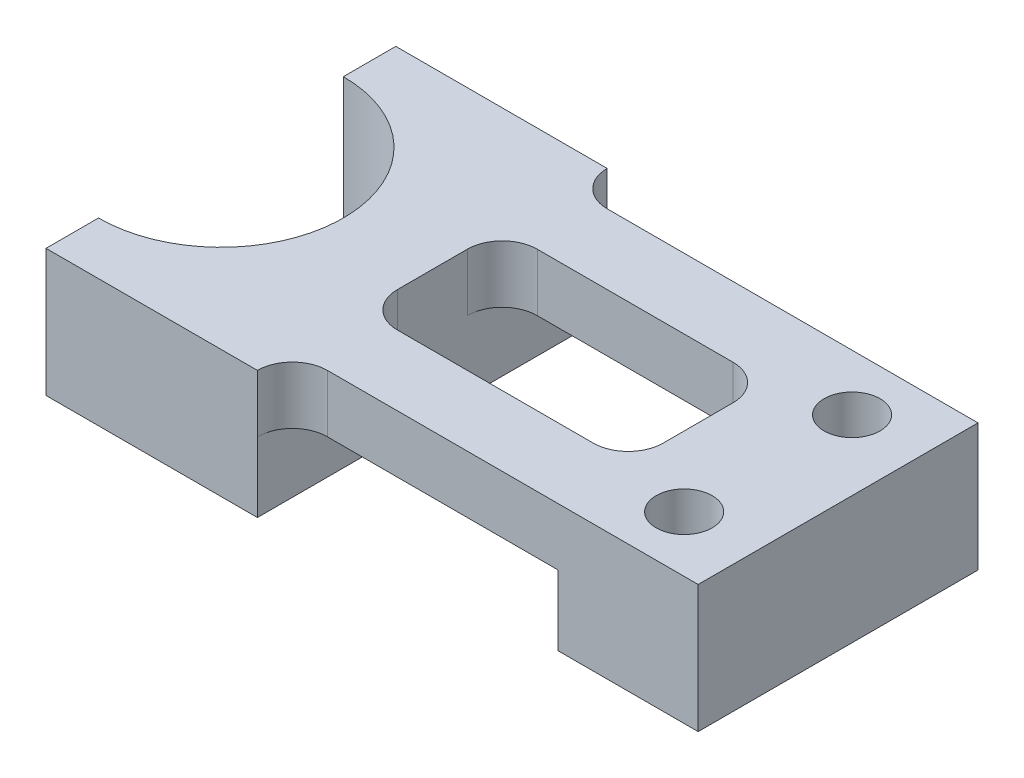
SolidWorks part; units mm, degrees
material "3.0205 (EN-AW 1200)"
ref_plane "Plan de face" through (0, 0, 0) normal (0, 0, 1) x (1, 0, 0)
ref_plane "Plan de dessus" through (0, 0, 0) normal (0, 1, 0) x (1, 0, 0)
ref_plane "Plan de droite" through (0, 0, 0) normal (1, 0, 0) x (0, 0, -1)
sketch "Esquisse1" plane through (0, 0, 0) normal (0, 1, 0) x (1, 0, 0)
  line L1 (-23.3581, -62.5798) -> (64.8619, -62.5798)
  line L2 (-23.3581, -62.5798) -> (-23.3581, -12.5798)
  line L3 (-23.3581, -12.5798) -> (64.8619, -12.5798)
  line L4 (64.8619, -62.5798) -> (64.8619, -12.5798)
  dimension "D1" = 88.22
  dimension "D2" = 50
extrude "Boss.-Extru.2" add sketch "Esquisse1" along normal blind 18.22
sketch "Esquisse3" plane through (0, 0, 0) normal (0, -1, 0) x (-1, 0, 0)
  line L0 (23.3581, -62.5798) -> (-64.8619, -62.5798) construction
  line L1 (-6.8619, -62.5798) -> (-44.8619, -62.5798)
  line L2 (-6.8619, -62.5798) -> (-6.8619, -12.5798)
  line L3 (-6.8619, -12.5798) -> (-44.8619, -12.5798)
  line L4 (-44.8619, -62.5798) -> (-44.8619, -12.5798)
  line L5 (-64.8619, -12.5798) -> (23.3581, -12.5798) construction
  dimension "D1" = 30.22
  dimension "D2" = 20
extrude "Enlèv. mat.-Extru.1" cut sketch "Esquisse3" against normal blind 10
sketch "Esquisse6" plane through (0, 0, 62.5798) normal (0, 0, 1) x (1, 0, 0)
  line L0 (-23.3581, 18.22) -> (64.8619, 18.22) construction
  line L1 (64.8619, 0) -> (6.8619, 0)
  line L2 (64.8619, 0) -> (64.8619, 18.22)
  line L3 (64.8619, 18.22) -> (6.8619, 18.22)
  line L4 (6.8619, 0) -> (6.8619, 18.22)
  line L5 (-23.3581, 18.22) -> (-23.3581, 0) construction
  dimension "D1" = 30.22
extrude "Enlèv. mat.-Extru.2" cut sketch "Esquisse6" against normal blind 5
sketch "Esquisse7" plane through (0, 0, 12.5798) normal (0, 0, -1) x (-1, 0, 0)
  line L0 (-64.8619, 18.22) -> (23.3581, 18.22) construction
  line L1 (-64.8619, 0) -> (-6.8619, 0)
  line L2 (-64.8619, 0) -> (-64.8619, 18.22)
  line L3 (-64.8619, 18.22) -> (-6.8619, 18.22)
  line L4 (-6.8619, 0) -> (-6.8619, 18.22)
  dimension "D1" = 30.22
extrude "Enlèv. mat.-Extru.3" cut sketch "Esquisse7" against normal blind 5
fillet "Congé6" radius 5 1 edges at (6.8619, 14.11, 17.5798)
fillet "Congé11" radius 5 1 edges at (6.8619, 14.11, 57.5798)
sketch "Esquisse8" plane through (0, 18.22, 0) normal (0, 1, 0) x (1, 0, 0)
  line L0 (-23.3581, -12.5798) -> (-23.3581, -62.5798) construction
  circle A0 centre (-23.3581, -37.5798) radius 17.5
  dimension "D2" = 35
  dimension "D1" = 25
extrude "Enlèv. mat.-Extru.4" cut sketch "Esquisse8" against normal through all
sketch "Esquisse10" plane through (0, 18.22, 0) normal (0, 1, 0) x (1, 0, 0)
  line L0 (64.8619, -57.5798) -> (64.8619, -17.5798) construction
  line L1 (44.8619, -47.5798) -> (6.8619, -47.5798)
  line L2 (44.8619, -47.5798) -> (44.8619, -27.5798)
  line L3 (44.8619, -27.5798) -> (6.8619, -27.5798)
  line L4 (6.8619, -47.5798) -> (6.8619, -27.5798)
  line L6 (64.8619, -57.5798) -> (11.8619, -57.5798) construction
  dimension "D1" = 20
  dimension "D2" = 10
  dimension "D3" = 10
  dimension "D4" = 38
extrude "Enlèv. mat.-Extru.5" cut sketch "Esquisse10" against normal through all
fillet "Congé7" radius 5 1 edges at (6.8619, 14.11, 27.5798)
fillet "Congé8" radius 5 1 edges at (6.8619, 14.11, 47.5798)
fillet "Congé9" radius 5 1 edges at (44.8619, 14.11, 27.5798)
fillet "Congé10" radius 5 1 edges at (44.8619, 14.11, 47.5798)
sketch "Esquisse11" plane through (0, 18.22, 0) normal (0, 1, 0) x (1, 0, 0)
  line L0 (64.8619, -57.5798) -> (11.8619, -57.5798) construction
  line L1 (11.8619, -17.5798) -> (64.8619, -17.5798) construction
  line L2 (64.8619, -57.5798) -> (64.8619, -17.5798) construction
  circle A0 centre (54.8619, -49.5798) radius 4
  circle A1 centre (54.8619, -25.5798) radius 4
  dimension "D1" = 8
  dimension "D2" = 8
  dimension "D3" = 8
  dimension "D4" = 8
  dimension "D5" = 10
  dimension "D6" = 10
extrude "Enlèv. mat.-Extru.6" cut sketch "Esquisse11" against normal through all
